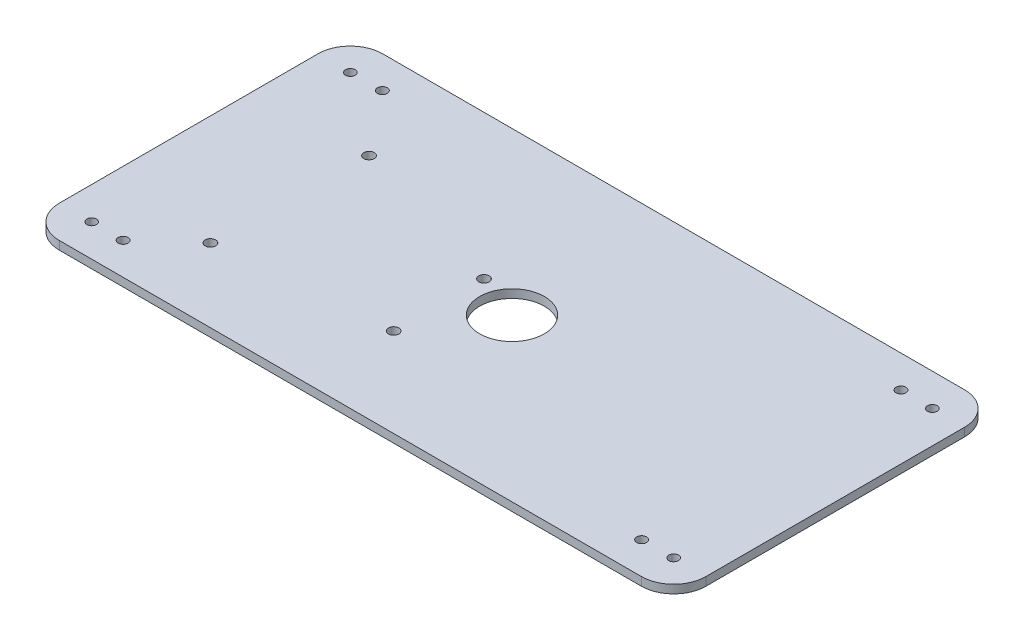
SolidWorks part; units mm, degrees
ref_plane "Front Plane" through (0, 0, 0) normal (0, 0, 1) x (1, 0, 0)
ref_plane "Top Plane" through (0, 0, 0) normal (0, 1, 0) x (1, 0, 0)
ref_plane "Right Plane" through (0, 0, 0) normal (1, 0, 0) x (0, 0, -1)
sketch "Sketch1" plane through (0, 0, 0) normal (0, 1, 0) x (1, 0, 0)
  line L1 (0, 0) -> (200, 0)
  line L2 (0, 0) -> (0, -100)
  line L3 (0, -100) -> (200, -100)
  line L4 (200, 0) -> (200, -100)
  dimension "D1" = 100
  dimension "D2" = 200
extrude "Boss-Extrude1" add sketch "Sketch1" along normal blind 2.6 contours L1 L4 L3 L2
fillet "Fillet1" radius 10 4 edges at (0, 1.3, 0) (0, 1.3, 100) (200, 1.3, 100) (200, 1.3, 0)
sketch "Sketch6" plane through (0, 0, 0) normal (0, -1, 0) x (1, 0, 0)
  line L0 (200, 10) -> (200, 90) construction
  line L1 (10, 0) -> (190, 0) construction
  circle A0 centre (190, 10) radius 1.5
  dimension "D1" = 3
  dimension "D2" = 10
  dimension "D3" = 10
ref_plane "Plane1" through (100, 0, 0) normal (1, 0, 0) x (0, 0, -1)
extrude "Cut-Extrude6" cut sketch "Sketch6" against normal blind 2.6 contours A0
ref_plane "Plane14" through (0, 0, 50) normal (0, 0, 1) x (1, 0, 0)
mirror "Mirror5" about plane through (100, 0, 0) normal (1, 0, 0) of "Cut-Extrude6"
mirror "Mirror6" about plane through (0, 0, 50) normal (0, 0, 1) of "Mirror5"
sketch "Sketch15" plane through (0, 0, 0) normal (0, -1, 0) x (1, 0, 0)
  line L0 (100, 0) -> (100, 100) construction
  line L2 (0, 50) -> (200, 50) construction
  line L4 (0, 10) -> (0, 90) construction
  line L5 (200, 10) -> (200, 90) construction
  line L6 (10, 0) -> (190, 0) construction
  line L7 (10, 100) -> (190, 100) construction
  circle A0 centre (100, 50) radius 10
  dimension "D1" = 20
sketch "Sketch16" plane through (0, 2.6, 0) normal (0, 1, 0) x (1, 0, 0)
  circle A0 centre (35.1575, -29.3715) radius 1.6192
extrude "Cut-Extrude9" cut sketch "Sketch16" against normal blind 10
sketch "Sketch17" plane through (0, 2.6, 0) normal (0, 1, 0) x (1, 0, 0)
  circle A0 centre (85.9447, -44.6115) radius 1.6193
extrude "Cut-Extrude10" cut sketch "Sketch17" against normal through all
sketch "Sketch18" plane through (0, 2.6, 0) normal (0, 1, 0) x (1, 0, 0)
  circle A0 centre (34.0145, -77.2886) radius 1.6193
extrude "Cut-Extrude11" cut sketch "Sketch18" against normal through all
sketch "Sketch19" plane through (0, 2.6, 0) normal (0, 1, 0) x (1, 0, 0)
  circle A0 centre (85.9447, -72.5387) radius 1.6193
extrude "Cut-Extrude12" cut sketch "Sketch19" against normal through all
extrude "Cut-Extrude14" cut sketch "Sketch15" against normal through all contours A0
sketch "Sketch23" plane through (0, 2.6, 0) normal (0, 1, 0) x (1, 0, 0)
  circle A0 centre (19.812, -9.906) radius 1.524
  point P2 (0, 0)
extrude "Cut-Extrude15" cut sketch "Sketch23" against normal blind 2.6
mirror "Mirror7" about plane through (100, 0, 0) normal (1, 0, 0) of "Cut-Extrude15"
mirror "Mirror8" about plane through (0, 0, 50) normal (0, 0, 1) of "Mirror7"
